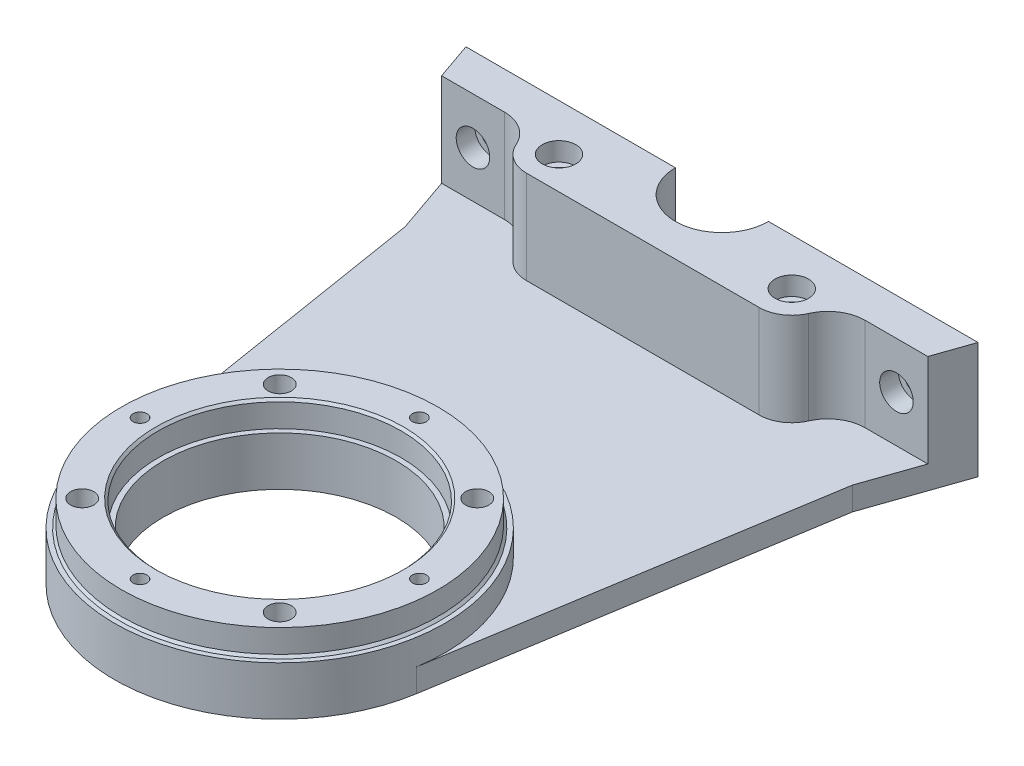
SolidWorks part; units mm, degrees
ref_plane "Front Plane" through (0, 0, 0) normal (0, 0, 1) x (1, 0, 0)
ref_plane "Top Plane" through (0, 0, 0) normal (0, 1, 0) x (1, 0, 0)
ref_plane "Right Plane" through (0, 0, 0) normal (1, 0, 0) x (0, 0, -1)
sketch "Sketch1" plane through (0, 0, 0) normal (0, 1, 0) x (1, 0, 0)
  circle A0 centre (0, 0) radius 34
  circle A1 centre (0, 0) radius 26.1
  dimension "D1" = 68
  dimension "D2" = 52.2
extrude "Boss-Extrude1" add sketch "Sketch1" along normal blind 5.5
sketch "Sketch2" plane through (0, 0, 0) normal (0, -1, 0) x (-1, 0, 0)
  circle A0 centre (0, 0) radius 35.5
  circle A1 centre (0, 0) radius 25
  dimension "D1" = 71
  dimension "D2" = 50
extrude "Boss-Extrude2" add sketch "Sketch2" along normal blind 5.5
sketch "Sketch3" plane through (0, -5.5, 0) normal (0, -1, 0) x (1, 0, 0)
  line L0 (-55, -95) -> (-10, -95)
  line L1 (-55, -95) -> (-48.055, -75)
  line L2 (55, -95) -> (48.055, -75)
  line L3 (-48.055, -75) -> (-35.0471, 5.6525)
  line L4 (48.055, -75) -> (35.0471, 5.6525)
  line L5 (10, -95) -> (55, -95)
  arc A0 (10, -95) -> (-10, -95) centre (0, -95) ccw
  circle A1 centre (0, 0) radius 25 construction
  circle A2 centre (0, 0) radius 35.5 construction
  circle A3 centre (0, 0) radius 25
  arc A4 (35.0471, 5.6525) -> (-35.0471, 5.6525) centre (0, 0) ccw
  circle A5 centre (-25, -85) radius 2.2
  circle A6 centre (25, -85) radius 2.2
  dimension "D9" = 4.4
  dimension "D10" = 20
  dimension "D1" = 95
  dimension "D2" = 96.11
  dimension "D3" = 110
  dimension "D4" = 6.945
  dimension "D5" = 20
  dimension "D6" = 25
  dimension "D7" = 50
  dimension "D8" = 10
extrude "Boss-Extrude3" add sketch "Sketch3" along normal blind 5 contours L3 A4 L4 L2 L5 A0 L0 L1 | A5 | A6 | A3
chamfer "Chamfer1" distance 0.5 angle 45 2 edges at (0, 0, 34) (0, 5.5, 26.1)
sketch "Sketch5" plane through (0, 5.5, 0) normal (0, 1, 0) x (1, 0, 0)
  line L0 (0, 0) -> (0, 30) construction
  line L1 (0, 0) -> (21.2132, 21.2132) construction
  circle A4 centre (21.2132, 21.2132) radius 2.5
  circle A5 centre (0, 30) radius 1.5
  circle A6 centre (30, 0) radius 1.5
  circle A7 centre (0, -30) radius 1.5
  circle A8 centre (-30, 0) radius 1.5
  circle A9 centre (21.2132, -21.2132) radius 2.5
  circle A10 centre (-21.2132, -21.2132) radius 2.5
  circle A11 centre (-21.2132, 21.2132) radius 2.5
  point P12 (0, 0)
  point P22 (0, 0)
  dimension "D1" = 30
  dimension "D3" = 3
  dimension "D6" = 5
  dimension "D2" = 4
  dimension "D4" = 45
  dimension "D5" = 30
  dimension "D7" = 4
extrude "Cut-Extrude1" cut sketch "Sketch5" against normal through all
sketch "Sketch6" plane through (0, -5.5, 0) normal (0, 1, 0) x (1, 0, 0)
  line L0 (55, 95) -> (48.055, 75) construction
  line L1 (10, 95) -> (55, 95) construction
  line L2 (-55, 95) -> (-48.055, 75) construction
  line L3 (-55, 95) -> (-10, 95) construction
  line L4 (55, 95) -> (52.222, 87)
  line L5 (10, 95) -> (55, 95)
  line L6 (-55, 95) -> (-52.222, 87)
  line L7 (-55, 95) -> (-10, 95)
  line L8 (-48.055, 75) -> (48.055, 75)
  line L9 (-52.222, 87) -> (-38.7477, 87)
  line L10 (-25, 78) -> (25, 78)
  line L11 (38.7477, 87) -> (52.222, 87)
  circle A0 centre (25, 85) radius 2.2 construction
  circle A1 centre (-25, 85) radius 2.2 construction
  circle A2 centre (25, 85) radius 2.2
  circle A3 centre (-25, 85) radius 2.2
  arc A4 (-31.4156, 82.2) -> (-25, 78) centre (-25, 85) ccw
  arc A5 (25, 78) -> (31.4156, 82.2) centre (25, 85) ccw
  arc A6 (31.4156, 82.2) -> (38.7477, 87) centre (38.7477, 79) cw
  arc A7 (-38.7477, 87) -> (-31.4156, 82.2) centre (-38.7477, 79) cw
  point P20 (31.7082, 87)
  circle M1 centre (25, 85) radius 2.2
  circle M2 centre (-25, 85) radius 2.2
  line M6 (48.055, 75) -> (55, 95)
  line M7 (55, 95) -> (10, 95)
  arc M8 (10, 95) -> (-10, 95) centre (0, 95) cw
  line M9 (-10, 95) -> (-55, 95)
  line M10 (-55, 95) -> (-48.055, 75)
  dimension "D1" = 14
  dimension "D3" = 8
  dimension "D2" = 8
extrude "Boss-Extrude4" add sketch "Sketch6" along normal blind 20 contours L8 M10 M6 M7 M8 M9 M2 M1 region at (52.5595, -5.5, -91.3651)
sketch "Sketch7" plane through (0, 14.5, 0) normal (0, 1, 0) x (1, 0, 0)
  circle A0 centre (25, 85) radius 3.6
  circle A1 centre (-25, 85) radius 3.6
  dimension "D1" = 7.2
extrude "Cut-Extrude2" cut sketch "Sketch7" against normal blind 4
sketch "Sketch8" plane through (0, 0, -87) normal (0, 0, 1) x (1, 0, 0)
  line L0 (-52.222, 14.5) -> (-52.222, -5.5) construction
  line L1 (-52.222, 14.5) -> (-38.7477, 14.5) construction
  line L2 (0, 0) -> (0, 23.5197) construction
  circle A0 centre (-45.4849, 4.5) radius 2.2
  circle A1 centre (45.4849, 4.5) radius 2.2
  point P4 (-52.222, 4.5)
  point P7 (-45.4849, 14.5)
  dimension "D1" = 4.4
extrude "Cut-Extrude3" cut sketch "Sketch8" against normal blind 8
sketch "Sketch9" plane through (0, 0, -87) normal (0, 0, 1) x (1, 0, 0)
  circle A0 centre (-45.4849, 4.5) radius 3.6
  circle A1 centre (45.4849, 4.5) radius 3.6
  dimension "D1" = 7.2
extrude "Cut-Extrude4" cut sketch "Sketch9" against normal blind 4
